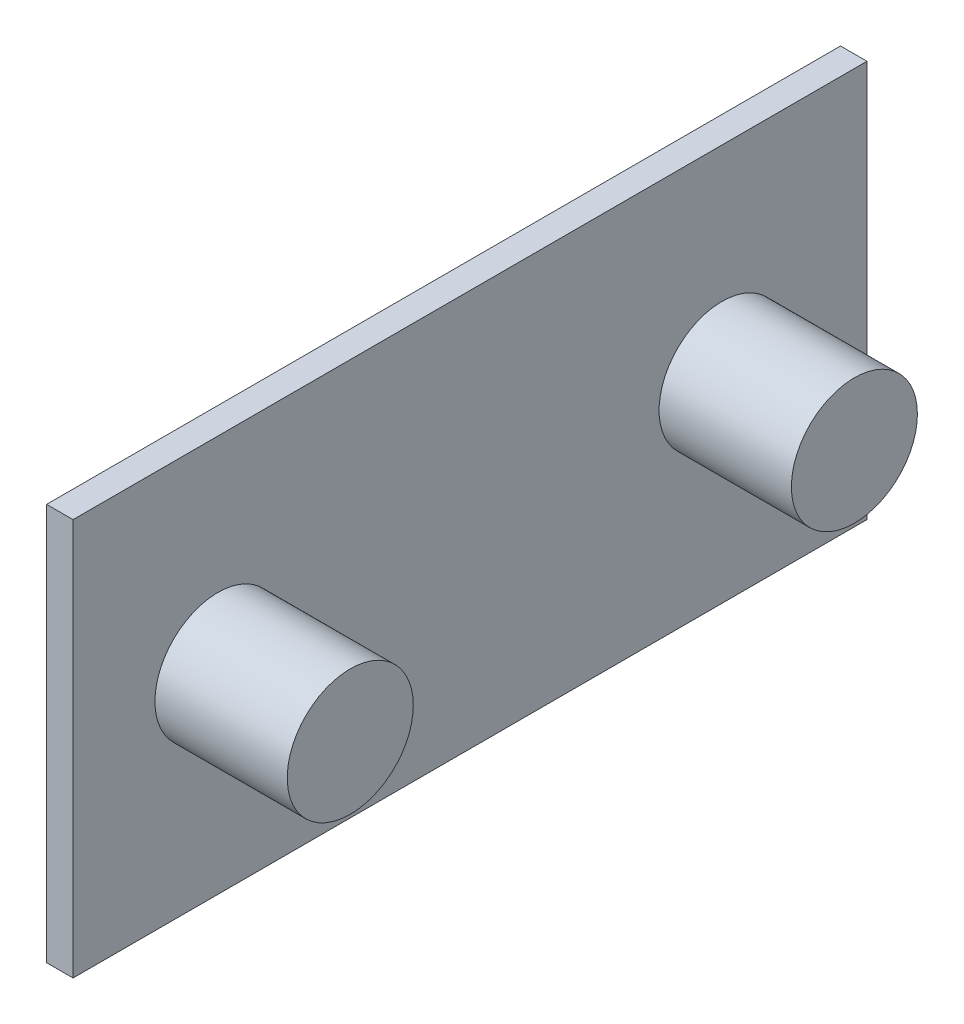
SolidWorks part; units mm, degrees
ref_plane "Front Plane" through (0, 0, 0) normal (0, 0, 1) x (1, 0, 0)
ref_plane "Top Plane" through (0, 0, 0) normal (0, 1, 0) x (1, 0, 0)
ref_plane "Right Plane" through (0, 0, 0) normal (1, 0, 0) x (0, 0, -1)
sketch "Sketch2" plane through (0, 0, 0) normal (1, 0, 0) x (0, 0, -1)
  line L0 (-30, 0) -> (30, 0) construction
  line L1 (30, 15) -> (-30, 15)
  line L2 (30, 15) -> (30, -15)
  line L3 (30, -15) -> (-30, -15)
  line L4 (-30, 15) -> (-30, -15)
  line L5 (30, 15) -> (-30, -15) construction
  line L6 (30, -15) -> (-30, 15) construction
  circle A0 centre (-19.05, 0) radius 4.7625
  circle A1 centre (19.05, 0) radius 4.7625
  point P0 (0, 0)
  point P12 (0, 0)
  dimension "D3" = 9.525
  dimension "D4" = 9.525
  dimension "D1" = 30
  dimension "D2" = 60
  dimension "D5" = 38.1
  dimension "D6" = 19.05
extrude "Boss-Extrude1" add sketch "Sketch2" along normal blind 2 contours A0 | A1 | L1 L4 L3 L2 A1 A0 region at (0, 0, 0) region at (0, 0, 19.05) region at (0, 0, -19.05)
extrude "Boss-Extrude2" add sketch "Sketch2<3>" along normal blind 10 from surface contours A0 | A1 region at (0, 0, 19.05) region at (0, 0, -19.05) starting at face at (2, 0, 0)
sketch "Sketch2<3>" plane through (0, 0, 0) normal (1, 0, 0) x (0, 0, -1) same geometry as "Sketch2"
